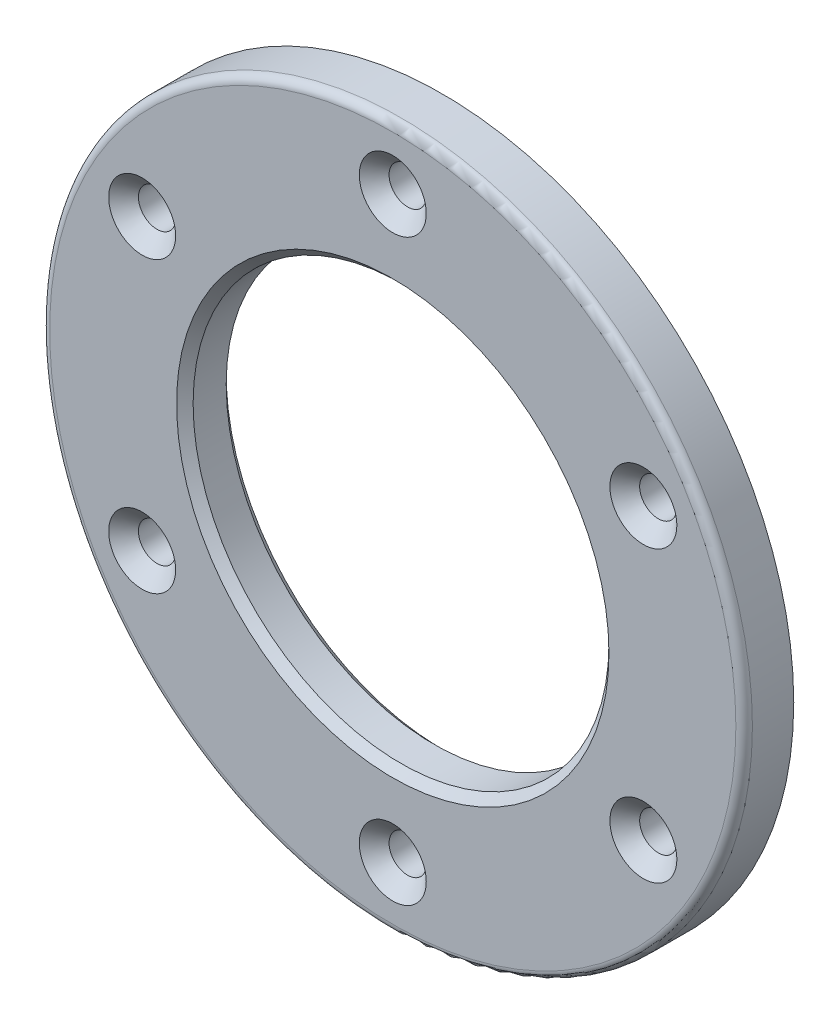
SolidWorks part; units mm, degrees
ref_plane "Front Plane" through (0, 0, 0) normal (0, 0, 1) x (1, 0, 0)
ref_plane "Top Plane" through (0, 0, 0) normal (0, 1, 0) x (1, 0, 0)
ref_plane "Right Plane" through (0, 0, 0) normal (1, 0, 0) x (0, 0, -1)
sketch "Sketch1" plane through (0, 0, 0) normal (0, 0, 1) x (1, 0, 0)
  circle A0 centre (0, 0) radius 42.5
  dimension "D1" = 85
extrude "Boss-Extrude1" add sketch "Sketch1" along normal blind 6
sketch "Sketch2" plane through (0, 0, 6) normal (0, 0, 1) x (1, 0, 0)
  circle A0 centre (0, 0) radius 25.15
  dimension "D1" = 50.3
extrude "Cut-Extrude1" cut sketch "Sketch2" against normal through all
sketch "Sketch3" plane through (0, 0, 6) normal (0, 0, 1) x (1, 0, 0)
  line L0 (0, 0) -> (0, 42.5) construction
  circle A0 centre (0, 0) radius 42.5 construction
  circle A1 centre (0, 35) radius 2.25
  dimension "D1" = 4.5
  dimension "D2" = 35
extrude "Cut-Extrude2" cut sketch "Sketch3" against normal through all
chamfer "Chamfer2" distance 1.8 angle 45 1 edges at (2.25, 35, 6)
pattern_circular "CirPattern1" count 6 over 360 about axis through (0, 0, 6) along (0, 0, -1) of "Cut-Extrude2", "Chamfer2"
chamfer "Chamfer1" distance 1 angle 45 2 edges at (25.15, 0, 0) (25.15, 0, 6)
fillet "Fillet1" radius 1 1 edges at (42.5, 0, 6)
